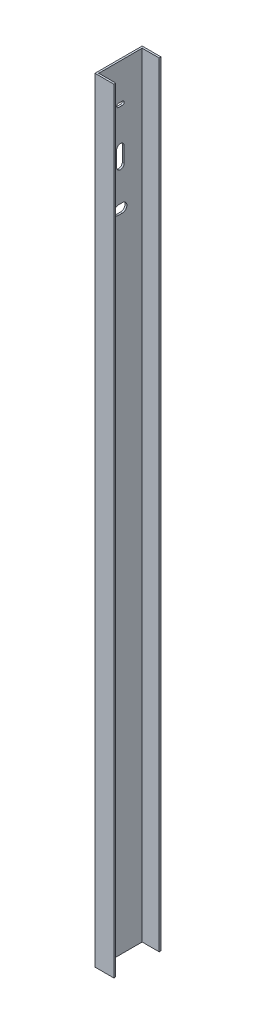
SolidWorks part; units mm, degrees
ref_plane "Front Plane" through (0, 0, 0) normal (0, 0, 1) x (1, 0, 0)
ref_plane "Top Plane" through (0, 0, 0) normal (0, 1, 0) x (1, 0, 0)
ref_plane "Right Plane" through (0, 0, 0) normal (1, 0, 0) x (0, 0, -1)
sketch "Sketch1" plane through (0, 0, 0) normal (0, 1, 0) x (1, 0, 0)
  line L1 (0, 0) -> (10, 0)
  line L2 (0, 0) -> (0, -25)
  line L3 (0, -25) -> (10, -25)
  line L4 (10, 0) -> (10, -25)
  dimension "D1" = 25
  dimension "D2" = 10
extrude "Boss-Extrude1" add sketch "Sketch1" along normal blind 410
sketch "Sketch2" plane through (0, 410, 0) normal (0, 1, 0) x (1, 0, 0)
  line L0 (10, -25) -> (10, 0) construction
  line L1 (10, -1) -> (1, -1)
  line L2 (10, -1) -> (10, -24)
  line L3 (10, -24) -> (1, -24)
  line L4 (1, -1) -> (1, -24)
  line L5 (10, 0) -> (0, 0) construction
  line L6 (0, -25) -> (10, -25) construction
  line L7 (0, 0) -> (0, -25) construction
  dimension "D1" = 1
  dimension "D2" = 1
  dimension "D3" = 1
extrude "Cut-Extrude1" cut sketch "Sketch2" against normal blind 410 contours L1 L4 L3 L2
sketch "Sketch3" plane through (0, 0, 0) normal (-1, 0, 0) x (0, 0, 1)
  line L0 (11.5, 390) -> (13.5, 390) construction
  line L1 (11.5, 391) -> (13.5, 391)
  line L2 (11.5, 389) -> (13.5, 389)
  line L3 (12.5, 370) -> (12.5, 362) construction
  line L4 (14.5, 370) -> (14.5, 362)
  line L5 (10.5, 370) -> (10.5, 362)
  line L6 (11.5, 342) -> (13.5, 342) construction
  line L7 (11.5, 344.4) -> (13.5, 344.4)
  line L8 (11.5, 339.6) -> (13.5, 339.6)
  line L9 (0, 410) -> (25, 410) construction
  line L10 (12.5, 410) -> (12.5, 405.5823) construction
  arc A0 (11.5, 391) -> (11.5, 389) centre (11.5, 390) ccw
  arc A1 (13.5, 389) -> (13.5, 391) centre (13.5, 390) ccw
  arc A2 (14.5, 370) -> (10.5, 370) centre (12.5, 370) ccw
  arc A3 (10.5, 362) -> (14.5, 362) centre (12.5, 362) ccw
  arc A4 (11.5, 344.4) -> (11.5, 339.6) centre (11.5, 342) ccw
  arc A5 (13.5, 339.6) -> (13.5, 344.4) centre (13.5, 342) ccw
  point P2 (12.5, 390)
  point P7 (12.5, 366)
  point P14 (12.5, 342)
  dimension "D4" = 1
  dimension "D6" = 2
  dimension "D9" = 2.4
  dimension "D1" = 20
  dimension "D2" = 20
  dimension "D3" = 2
  dimension "D5" = 8
  dimension "D7" = 20
  dimension "D8" = 2
extrude "Cut-Extrude2" cut sketch "Sketch3" against normal blind 410 contours L2 A1 L1 A0
extrude "Cut-Extrude3" cut sketch "Sketch3<3>" against normal blind 410 contours A2 L5 A3 L4
sketch "Sketch3<3>" plane through (0, 0, 0) normal (-1, 0, 0) x (0, 0, 1) same geometry as "Sketch3"
extrude "Cut-Extrude4" cut sketch "Sketch3<4>" against normal blind 410 contours L7 A5 L8 A4
sketch "Sketch3<4>" plane through (0, 0, 0) normal (-1, 0, 0) x (0, 0, 1) same geometry as "Sketch3"
